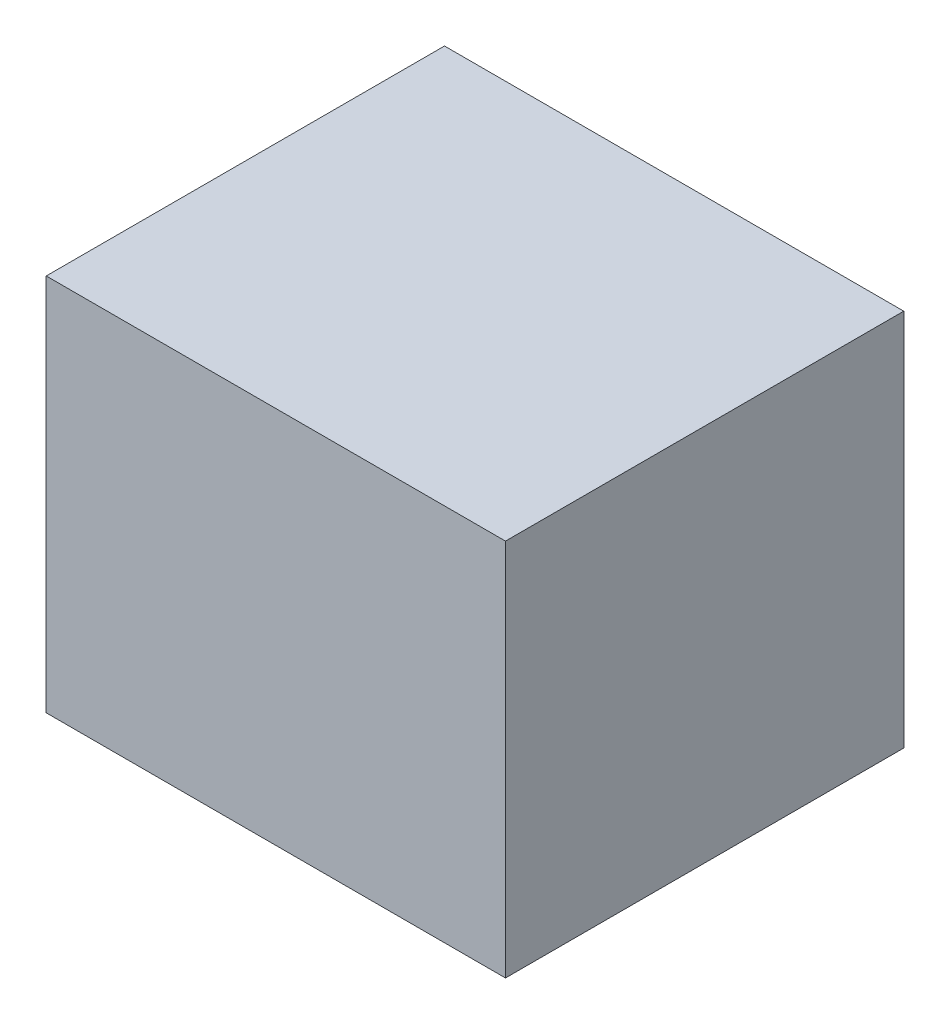
SolidWorks part; units mm, degrees
ref_plane "Front Plane" through (0, 0, 0) normal (0, 0, 1) x (1, 0, 0)
ref_plane "Top Plane" through (0, 0, 0) normal (0, 1, 0) x (1, 0, 0)
ref_plane "Right Plane" through (0, 0, 0) normal (1, 0, 0) x (0, 0, -1)
sketch "Sketch1" plane through (0, 0, 0) normal (0, 0, 1) x (1, 0, 0)
  line L0 (0, 0) -> (150.63, 0)
  line L1 (0, 0) -> (12.3, 88.9)
  line L2 (12.3, 88.9) -> (87.13, 88.9)
  line L3 (87.13, 88.9) -> (150.63, 0)
  dimension "D1" = 150.63
  dimension "D2" = 88.9
  dimension "D3" = 12.3
  dimension "D4" = 63.5
extrude "Boss-Extrude1" add sketch "Sketch1" along normal blind 4.765 and the other way blind 4.765
sketch "Sketch2" plane through (0, 0, 0) normal (0, -1, 0) x (1, 0, 0)
  line L0 (150.63, 0) -> (133.34, 4.765)
  line L1 (150.63, -4.765) -> (150.63, 4.765) construction
  line L2 (0, 4.765) -> (150.63, 4.765) construction
  line L3 (150.63, 0) -> (133.34, -4.765)
  line L4 (0, -4.765) -> (150.63, -4.765) construction
  line L5 (133.34, 4.765) -> (171.6703, 17.6987)
  line L6 (171.6703, 17.6987) -> (171.0055, -7.6445)
  line L7 (171.0055, -7.6445) -> (148.072, -23.349)
  line L8 (148.072, -23.349) -> (133.34, -4.765)
  dimension "D1" = 17.29
extrude "Cut-Extrude1" cut sketch "Sketch2" along direction (-0.5812, 0.8137, 0) on the side against the normal up to surface (88.9 mm away) up to face at (49.715, 88.9, 0)
sketch "Sketch3" plane through (0, 0, 4.765) normal (0, 0, 1) x (1, 0, 0)
  line L0 (10.9295, 78.9944) -> (7.4484, 53.834)
  line L1 (10.9295, 78.9944) -> (29.7997, 76.3835)
  line L2 (7.4484, 53.834) -> (26.3186, 51.2232)
  line L3 (29.7997, 76.3835) -> (26.3186, 51.2232)
  line L4 (12.3, 88.9) -> (0, 0) construction
  line M8 (12.3, 88.9) -> (0, 0)
  dimension "D1" = 19.05
  dimension "D2" = 25.4
  dimension "D3" = 10
extrude "Cut-Extrude2" cut sketch "Sketch3" against normal through all contours L3 L1 L2 M8 region at (18.624, 65.1088, 4.765)
sketch "Sketch4" plane through (10.9295, 78.9944, 0) normal (-0.1371, -0.9906, 0) x (0.9906, -0.1371, 0)
  line L0 (16.8545, -5.0685) -> (12.5906, -4.3167)
  line L1 (16.8545, -5.0685) -> (18.5094, 4.3167)
  line L2 (12.5906, -4.3167) -> (14.2455, 5.0685)
  line L3 (18.5094, 4.3167) -> (14.2455, 5.0685)
  line L4 (19.05, 4.765) -> (0, 4.765)
  line L5 (0, 4.765) -> (0, -4.765)
  line L6 (0, -4.765) -> (19.05, -4.765)
  line L7 (19.05, -4.765) -> (19.05, 4.765)
  line L8 (19.05, 4.765) -> (0, 4.765)
  line L9 (0, 4.765) -> (0, -4.765)
  line L10 (0, -4.765) -> (19.05, -4.765)
  line L11 (19.05, -4.765) -> (19.05, 4.765)
  line L12 (16.8545, -5.0685) -> (14.2455, 5.0685) construction
  line L13 (12.5906, -4.3167) -> (18.5094, 4.3167) construction
  line L14 (0, 0) -> (19.05, 0) construction
  line L15 (12.5906, -4.3167) -> (14.2455, 5.0685)
  line L16 (12.5906, -4.3167) -> (-1.9061, -1.7605)
  line L17 (14.2455, 5.0685) -> (-0.2512, 7.6247)
  line L18 (-1.9061, -1.7605) -> (-0.2512, 7.6247)
  circle A0 centre (15.55, 0) radius 3.5
  line M15 (19.05, 4.765) -> (0, 4.765)
  line M16 (0, 4.765) -> (0, -4.765)
  line M17 (0, -4.765) -> (19.05, -4.765)
  dimension "D2" = 10
  dimension "D3" = 7
  dimension "D4" = 9.53
  dimension "D5" = 19.05
  dimension "D1" = 0
extrude "Boss-Extrude2" add sketch "Sketch4" along normal up to surface (25.4 mm away) contours L18 L16 L2 L17 M16 M15 | A0 L2 L16 M15 M16 | L15 A0 | L1 A0 L15 | A0 L1 L3 L2 M15 | L3 L2 M15 | A0 L2 L0 L1 M17 | L0 L1 M17 region at (27.0742, 76.7606, -4.8662) region at (25.5834, 76.9669, -3.8966) region at (17.6027, 78.0711, 0.8374) region at (26.3327, 76.8632, 0) region at (23.6904, 77.2288, 0.4704) region at (10.0178, 79.1205, -1.7429) region at (27.082, 76.7595, 3.8966) region at (25.5913, 76.9658, 4.8662) up to face at (16.8835, 52.5286, 0)
sketch "Sketch5" plane through (17.0506, -2.3591, -3.0351) normal (0.9755, -0.135, -0.1736) x (-0.172, 0.0238, -0.9848)
  line L6 (1.7566, 54.3469) -> (2.0648, 54.3469)
  line L7 (2.0648, 54.3469) -> (2.0648, 79.7469)
  line L8 (2.0648, 79.7469) -> (1.7566, 79.7469)
  line L9 (1.7566, 79.7469) -> (-7.4652, 79.7469)
  line L10 (-7.4652, 79.7469) -> (-7.4652, 54.3469)
  line L11 (-7.4652, 54.3469) -> (1.7566, 54.3469)
  line L12 (1.7566, 54.3469) -> (2.0648, 54.3469)
  line L13 (2.0648, 54.3469) -> (2.0648, 79.7469)
  line L14 (2.0648, 79.7469) -> (1.7566, 79.7469)
  line L15 (1.7566, 79.7469) -> (-7.4652, 79.7469)
  line L16 (-7.4652, 79.7469) -> (-7.4652, 54.3469)
  line L17 (-7.4652, 54.3469) -> (1.7566, 54.3469)
  dimension "D1" = 0
extrude "Boss-Extrude3" add sketch "Sketch5" along direction (-1, 0, 0) on the side of the normal up to surface (0.5458 mm away) up to face at (28.0592, 63.8034, 0)
sketch "Sketch6" plane through (18.8702, -2.6108, 0) normal (-0.9906, 0.1371, 0) x (0, 0, 1)
  line L6 (4.765, 79.7469) -> (4.3167, 79.7469)
  line L7 (4.3167, 79.7469) -> (4.3167, 54.4217)
  line L8 (4.3167, 54.4217) -> (-4.765, 54.6432)
  line L9 (-4.765, 54.6432) -> (-4.765, 54.3469)
  line L10 (-4.765, 54.3469) -> (4.765, 54.3469)
  line L11 (4.765, 54.3469) -> (4.765, 79.7469)
  line L12 (4.765, 79.7469) -> (4.3167, 79.7469)
  line L13 (4.3167, 79.7469) -> (4.3167, 54.4217)
  line L14 (4.3167, 54.4217) -> (-4.765, 54.6432)
  line L15 (-4.765, 54.6432) -> (-4.765, 54.3469)
  line L16 (-4.765, 54.3469) -> (4.765, 54.3469)
  line L17 (4.765, 54.3469) -> (4.765, 79.7469)
  dimension "D1" = 0
extrude "Boss-Extrude4" add sketch "Sketch6" along normal up to surface up to face at (20.4896, 64.8507, 5.5688)
sketch "Sketch8" plane through (0, 88.9, 0) normal (0, 1, 0) x (1, 0, 0)
  line L0 (48.3099, 4.765) -> (18.8121, 4.765)
  line L1 (48.3099, 4.765) -> (48.3099, 16.5868)
  line L2 (18.8121, 4.765) -> (18.8121, 16.5868)
  line L3 (48.3099, 16.5868) -> (18.8121, 16.5868)
  line L5 (69.84, -4.765) -> (87.13, 0)
  line L6 (87.13, 0) -> (69.84, 4.765)
  line L7 (69.84, 4.765) -> (12.3, 4.765)
  line L8 (12.3, 4.765) -> (12.3, -4.765)
  line L9 (12.3, -4.765) -> (69.84, -4.765)
  line L10 (69.84, -4.765) -> (87.13, 0)
  line L11 (87.13, 0) -> (69.84, 4.765)
  line L12 (69.84, 4.765) -> (12.3, 4.765)
  line L13 (12.3, 4.765) -> (12.3, -4.765)
  line L14 (12.3, -4.765) -> (69.84, -4.765)
  line M8 (69.84, 4.765) -> (12.3, 4.765)
  dimension "D1" = 0
extrude "Cut-Extrude4" cut sketch "Sketch8" against normal through all both and the other way through all contours L1 L3 L2 M8 region at (33.561, 88.9, -10.6759)
sketch "Sketch9" plane through (18.8702, -2.6108, 0) normal (-0.9906, 0.1371, 0) x (0, 0, 1)
  line L4 (4.2214, 54.3469) -> (4.2214, 54.424)
  line L5 (4.2214, 54.424) -> (-4.765, 54.6432)
  line L6 (-4.765, 54.6432) -> (-4.765, 54.3469)
  line L7 (-4.765, 54.3469) -> (4.2214, 54.3469)
  line L8 (4.2214, 54.3469) -> (4.2214, 54.424)
  line L9 (4.2214, 54.424) -> (-4.765, 54.6432)
  line L10 (-4.765, 54.6432) -> (-4.765, 54.3469)
  line L11 (-4.765, 54.3469) -> (4.2214, 54.3469)
  dimension "D1" = 0
extrude "Boss-Extrude5" add sketch "Sketch9" along normal up to surface
sketch "Sketch10" plane through (0, 0, 0) normal (0, -1, 0) x (1, 0, 0)
  line L1 (-788.9516, -684.1945) -> (788.9516, -684.1945)
  line L2 (-788.9516, -684.1945) -> (-788.9516, 684.1945)
  line L3 (-788.9516, 684.1945) -> (788.9516, 684.1945)
  line L4 (788.9516, -684.1945) -> (788.9516, 684.1945)
  line L5 (150.63, 0) -> (133.34, 4.765)
  line L6 (133.34, 4.765) -> (0, 4.765)
  line L7 (0, 4.765) -> (0, -4.765)
  line L8 (0, -4.765) -> (133.34, -4.765)
  line L9 (133.34, -4.765) -> (150.63, 0)
  line L10 (150.63, 0) -> (133.34, 4.765)
  line L11 (133.34, 4.765) -> (0, 4.765)
  line L12 (0, 4.765) -> (0, -4.765)
  line L13 (0, -4.765) -> (133.34, -4.765)
  line L14 (133.34, -4.765) -> (150.63, 0)
  line L15 (-788.9516, -684.1945) -> (788.9516, 684.1945) construction
  line L16 (-788.9516, 684.1945) -> (788.9516, -684.1945) construction
  point P2 (0, 0)
  point P10 (572.3845, 347.994)
  point P11 (788.9516, 684.1945)
  line M10 (150.63, 0) -> (133.34, 4.765)
  line M11 (133.34, 4.765) -> (0, 4.765)
  line M12 (0, 4.765) -> (0, -4.765)
  line M13 (0, -4.765) -> (133.34, -4.765)
  line M14 (133.34, -4.765) -> (150.63, 0)
  dimension "D1" = 0
extrude "Boss-Extrude6" add sketch "Sketch10" against normal blind 1300 separate body contours L1 L4 L3 L2 M10 M14 M13 M12 M11 | M14 M10 M11 M12 M13 region at (-0.0446, 0, 0) region at (71.0802, 0, 0)
